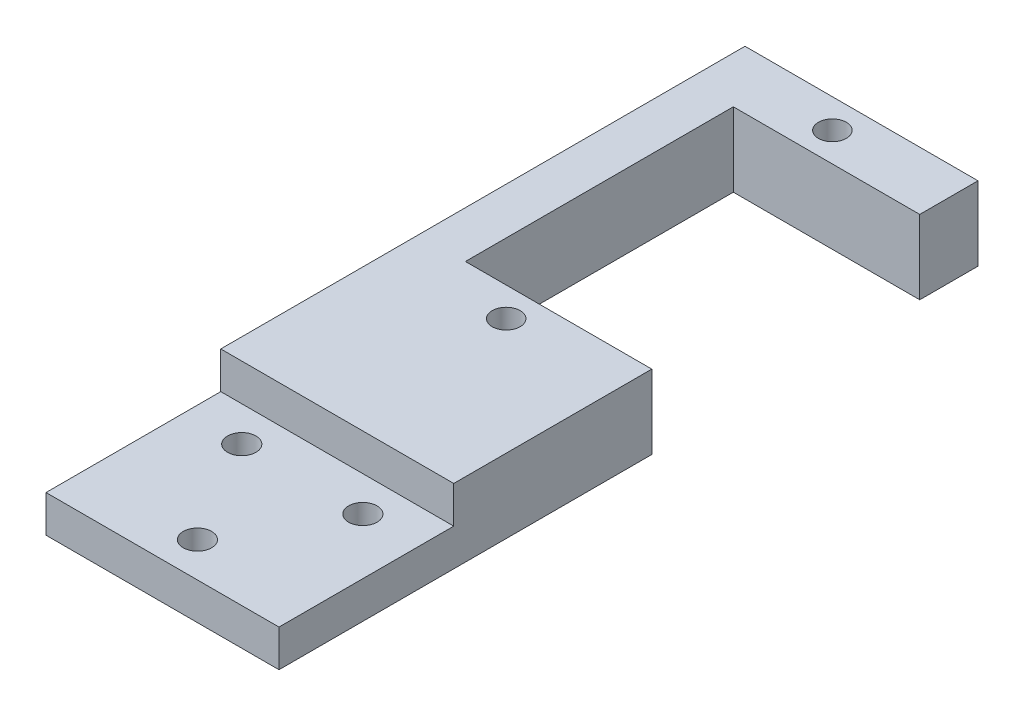
SolidWorks part; units mm, degrees
material "ABS"
ref_plane "Front" through (0, 0, 0) normal (0, 0, 1) x (1, 0, 0)
ref_plane "Top" through (0, 0, 0) normal (0, 1, 0) x (1, 0, 0)
ref_plane "Right" through (0, 0, 0) normal (1, 0, 0) x (0, 0, -1)
sketch "Sketch2" plane through (0, 0, 0) normal (0, 1, 0) x (1, 0, 0)
  line L1 (0, 0) -> (20, 0)
  line L2 (0, 0) -> (0, -60)
  line L3 (0, -60) -> (20, -60)
  line L4 (20, 0) -> (20, -60)
  dimension "D1" = 20
  dimension "D2" = 60
extrude "Boss-Extrude1" add sketch "Sketch2" along normal blind 6.35
sketch "Sketch4" plane through (0, 6.35, 0) normal (0, 1, 0) x (1, 0, 0)
  line L1 (4, -5) -> (20, -5)
  line L2 (4, -5) -> (4, -28)
  line L3 (4, -28) -> (20, -28)
  line L4 (20, -5) -> (20, -28)
  line L6 (20, 0) -> (0, 0) construction
  line L8 (0, 0) -> (0, -60) construction
  line L9 (20, -60) -> (20, 0) construction
  point P6 (0, 0)
  dimension "D1" = 4
  dimension "D2" = 5
  dimension "D3" = 23
extrude "Cut-Extrude1" cut sketch "Sketch4" against normal through all
hole_wizard "M2 Clearance Hole1" positions "Sketch8" profile "Sketch9" hole size "M2" standard "IS" end condition through all
sketch "Sketch8" plane through (0, 6.35, 0) normal (0, 1, 0) x (1, 0, 0)
  line L0 (10, 0) -> (10, -60) construction
  line L1 (20, 0) -> (0, 0) construction
  line L2 (0, -60) -> (20, -60) construction
  line L3 (4, -28) -> (20, -28) construction
  point P9 (10, -2.5)
  point P11 (10, -30.5)
  dimension "D1" = 2.5
  dimension "D2" = 2.5
sketch "Sketch9" plane through (10, 6.35, 30.5) normal (1, 0, 0) x (0, 0, 1)
  line L0 (0, 0) -> (0, 6.35)
  line L1 (0, 6.35) -> (1.2, 6.35)
  line L2 (1.2, 6.35) -> (1.2, 0)
  line L5 (1.2, 0) -> (0, 0)
  line L11 (0, -6.35) -> (0, 107.95) construction
  dimension "Thru Hole Dia." = 2.4
  dimension "Thru Hole Depth" = 6.35
sketch "Sketch10" plane through (20, 0, 0) normal (1, 0, 0) x (0, 0, -1)
  line L0 (-60, 6.35) -> (-60, 0) construction
  line L1 (-60, 6.35) -> (-45, 6.35)
  line L2 (-60, 6.35) -> (-60, 3.175)
  line L3 (-60, 3.175) -> (-45, 3.175)
  line L4 (-45, 6.35) -> (-45, 3.175)
  dimension "D1" = 15
extrude "Cut-Extrude2" cut sketch "Sketch10" against normal through all
sketch "Sketch12" plane through (0, 3.175, 0) normal (0, 1, 0) x (1, 0, 0)
  line L0 (10, -60) -> (10, -45) construction
  line L1 (0, -60) -> (20, -60) construction
  line L2 (0, -45) -> (20, -45) construction
  line L3 (10, -57) -> (15.1962, -48) construction
  line L4 (15.1962, -48) -> (4.8038, -48) construction
  line L5 (4.8038, -48) -> (10, -57) construction
  point P14 (5.8735, -60)
  dimension "D1" = 9
  dimension "D2" = 3
hole_wizard "#2 Clearance Hole1" positions "Sketch13" profile "Sketch14" hole size "#2" standard "ANSI Inch" end condition through all
sketch "Sketch13" plane through (0, 3.175, 0) normal (0, 1, 0) x (1, 0, 0)
  point P9 (4.8038, -48)
  point P12 (15.1962, -48)
  point P15 (10, -57)
  point P19 (0, 0)
  point P20 (0, 0)
  point P21 (0, 0)
sketch "Sketch14" plane through (4.8038, 3.175, 48) normal (1, 0, 0) x (0, 0, 1)
  line L0 (0, 0) -> (0, 3.175)
  line L1 (0, 3.175) -> (1.2192, 3.175)
  line L2 (1.2192, 3.175) -> (1.2192, 0)
  line L5 (1.2192, 0) -> (0, 0)
  line L11 (0, -6.35) -> (0, 107.95) construction
  dimension "Thru Hole Dia." = 2.4384
  dimension "Thru Hole Depth" = 3.175
